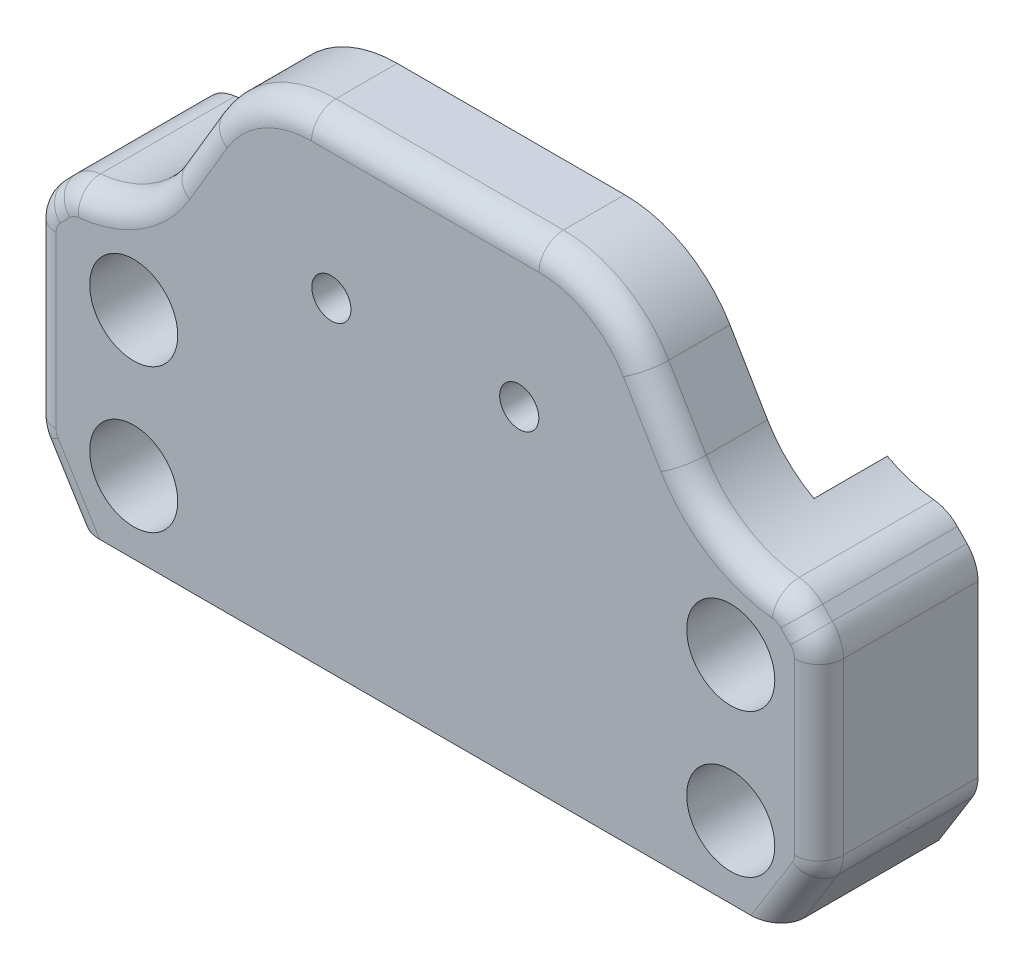
SolidWorks part; units mm, degrees
ref_plane "Front Plane" through (0, 0, 0) normal (0, 0, 1) x (1, 0, 0)
ref_plane "Top Plane" through (0, 0, 0) normal (0, 1, 0) x (1, 0, 0)
ref_plane "Right Plane" through (0, 0, 0) normal (1, 0, 0) x (0, 0, -1)
sketch "Sketch1" plane through (0, 0, 0) normal (0, 0, 1) x (1, 0, 0)
  line L16 (-28.9734, 12.7063) -> (28.9734, 12.7063)
  line L17 (32.1764, 18.7493) -> (32.1764, 32.6525)
  line L18 (31.2778, 34.8604) -> (30.4873, 35.6749)
  line L19 (20.9709, 41.4652) -> (17.9035, 46.6518)
  line L20 (9.2961, 51.5614) -> (-9.2961, 51.5614)
  line L21 (-17.9035, 46.6518) -> (-20.9709, 41.4652)
  line L22 (-30.4873, 35.6749) -> (-31.2778, 34.8604)
  line L23 (-32.1764, 32.6525) -> (-32.1764, 18.7493)
  arc A16 (-31.7074, 17.1064) -> (-28.9734, 12.7063) centre (10325.6911, 6449.6777) ccw
  arc A17 (28.9734, 12.7063) -> (31.7074, 17.1064) centre (-10325.6909, 6449.6776) ccw
  arc A18 (30.4873, 35.6749) -> (28.5623, 36.6074) centre (28.2447, 33.4985) ccw
  arc A19 (20.9709, 41.4652) -> (28.5623, 36.6074) centre (29.5783, 46.5556) ccw
  arc A20 (17.9035, 46.6518) -> (9.2961, 51.5614) centre (9.2961, 41.5614) ccw
  arc A21 (-9.2961, 51.5614) -> (-17.9035, 46.6518) centre (-9.2961, 41.5614) ccw
  arc A22 (-28.5623, 36.6074) -> (-20.9709, 41.4652) centre (-29.5783, 46.5556) ccw
  arc A23 (-28.5623, 36.6074) -> (-30.4873, 35.6749) centre (-28.2447, 33.4985) ccw
  spline S8 degree 3 poles (31.7074, 17.1064) (31.8606, 17.353) (31.9771, 17.6159) (32.1365, 18.1743) (32.1764, 18.459) (32.1764, 18.7493) knots 0 0 0 0 0.5 0.5 1 1 1 1
  spline S9 degree 3 poles (32.1764, 32.6525) (32.1764, 33.0639) (32.0982, 33.461) (31.8658, 34.0322) (31.7712, 34.2121) (31.5493, 34.5519) (31.4211, 34.7127) (31.2778, 34.8604) knots 0 0 0 0 0.5 0.5 0.75 0.75 1 1 1 1
  spline S10 degree 3 poles (-31.2778, 34.8604) (-31.5643, 34.5651) (-31.7861, 34.2264) (-32.0193, 33.6555) (-32.0775, 33.4608) (-32.156, 33.0628) (-32.1764, 32.8582) (-32.1764, 32.6525) knots 0 0 0 0 0.5 0.5 0.75 0.75 1 1 1 1
  spline S11 degree 3 poles (-32.1764, 18.7493) (-32.1764, 18.459) (-32.1365, 18.1742) (-31.9771, 17.6159) (-31.8606, 17.353) (-31.7074, 17.1064) knots 0 0 0 0 0.5 0.5 1 1 1 1
extrude "Boss-Extrude1" add sketch "Sketch1" along normal blind 13
shell "Shell1" thickness 3 removed face at (-0.0757, 32.8443, 0)
sketch "Sketch6" plane through (0, 0, 0) normal (0, 0, -1) x (-1, 0, 0)
  line L0 (-18.5324, 45.5884) -> (-18.5324, 12.7063)
  line L1 (28.9734, 12.7063) -> (18.5324, 12.7063)
  line L2 (32.1764, 32.6525) -> (32.1764, 18.7493)
  line L3 (30.4873, 35.6749) -> (31.2778, 34.8604)
  line L5 (18.5324, 45.5884) -> (20.9709, 41.4652)
  line L15 (18.5324, 45.5884) -> (18.5324, 12.7063)
  line L19 (32.1764, 18.7493) -> (32.1764, 32.6525)
  line L20 (31.2778, 34.8604) -> (30.4873, 35.6749)
  line L21 (20.9709, 41.4652) -> (17.9035, 46.6518)
  line L22 (9.2961, 51.5614) -> (-9.2961, 51.5614)
  line L23 (-17.9035, 46.6518) -> (-20.9709, 41.4652)
  line L24 (-30.4873, 35.6749) -> (-31.2778, 34.8604)
  line L25 (-32.1764, 32.6525) -> (-32.1764, 18.7493)
  line L26 (-28.9734, 12.7063) -> (28.9734, 12.7063)
  line L32 (-30.4873, 35.6749) -> (-31.2778, 34.8604)
  line L33 (-32.1764, 32.6525) -> (-32.1764, 18.7493)
  line L34 (-28.9734, 12.7063) -> (-18.5324, 12.7063)
  line L39 (-18.5324, 45.5884) -> (-20.9709, 41.4652)
  arc A0 (31.7074, 17.1064) -> (28.9734, 12.7063) centre (-10325.6909, 6449.6776) cw
  arc A1 (28.5623, 36.6074) -> (30.4873, 35.6749) centre (28.2447, 33.4985) cw
  arc A3 (28.5623, 36.6074) -> (20.9709, 41.4652) centre (29.5783, 46.5556) cw
  arc A24 (30.4873, 35.6749) -> (28.5623, 36.6074) centre (28.2447, 33.4985) ccw
  arc A25 (20.9709, 41.4652) -> (28.5623, 36.6074) centre (29.5783, 46.5556) ccw
  arc A27 (17.9035, 46.6518) -> (9.2961, 51.5614) centre (9.2961, 41.5614) ccw
  arc A28 (-28.5623, 36.6074) -> (-20.9709, 41.4652) centre (-29.5783, 46.5556) ccw
  arc A29 (-28.5623, 36.6074) -> (-30.4873, 35.6749) centre (-28.2447, 33.4985) ccw
  arc A30 (-31.7074, 17.1064) -> (-28.9734, 12.7063) centre (10325.6909, 6449.6776) ccw
  arc A31 (28.9734, 12.7063) -> (31.7074, 17.1064) centre (-10325.6911, 6449.6777) ccw
  arc A36 (-28.5623, 36.6074) -> (-20.9709, 41.4652) centre (-29.5783, 46.5556) ccw
  arc A37 (-28.5623, 36.6074) -> (-30.4873, 35.6749) centre (-28.2447, 33.4985) ccw
  arc A38 (-31.7074, 17.1064) -> (-28.9734, 12.7063) centre (10325.6909, 6449.6776) ccw
  arc A41 (-9.2961, 51.5614) -> (-17.9035, 46.6518) centre (-9.2961, 41.5614) ccw
  spline S0 degree 3 poles (32.1764, 18.7493) (32.1764, 18.459) (32.1365, 18.1743) (31.9771, 17.6159) (31.8606, 17.353) (31.7074, 17.1064) knots 0 0 0 0 0.5 0.5 1 1 1 1
  spline S1 degree 3 poles (31.2778, 34.8604) (31.4211, 34.7127) (31.5493, 34.5519) (31.7712, 34.2121) (31.8658, 34.0322) (32.0982, 33.461) (32.1764, 33.0639) (32.1764, 32.6525) knots 0 0 0 0 0.25 0.25 0.5 0.5 1 1 1 1
  spline S6 degree 3 poles (-912.5791, 346.2308) (-318.4122, 113.0842) (24.4464, -8.7582) (39.2445, 43.0679) (-277.4576, 113.683) (-947.6945, 218.3407) knots -47.236117 -47.236117 -47.236117 -47.236117 0.5 0.5 45.584579 45.584579 45.584579 45.584579 only from (31.7074, 17.1064) to (32.1764, 18.7493)
  spline S7 degree 3 poles (-468.469, 898.3041) (-31.3897, -10.7843) (34.4741, 21.3175) (32.0775, 33.4608) (32.0193, 33.6555) (21.9253, 58.367) (-263.5849, -90.6627) (-388.758, -872.6435) knots -14.755305 -14.755305 -14.755305 -14.755305 0.25 0.25 0.5 0.5 32.717715 32.717715 32.717715 32.717715 only from (32.1764, 32.6525) to (31.2778, 34.8604)
  spline S8 degree 3 poles (-1112.7848, -2759.5108) (116.981, -4.4034) (-22.0681, 49.0741) (-31.7712, 34.2121) (-31.8658, 34.0322) (-45.7307, -0.0443) (547.9859, -163.1479) (2818.0682, 896.9495) knots -21.365975 -21.365975 -21.365975 -21.365975 0.25 0.25 0.5 0.5 44.99757 44.99757 44.99757 44.99757 only from (-31.2778, 34.8604) to (-32.1764, 32.6525)
  spline S9 degree 3 poles (2916.7276, 565.2774) (892.1774, 236.9438) (-44.3588, 60.9799) (-18.3881, -29.9762) (1076.9235, 400.8267) (2716.3284, 1214.7036) knots -76.665281 -76.665281 -76.665281 -76.665281 0.5 0.5 86.237754 86.237754 86.237754 86.237754 only from (-32.1764, 18.7493) to (-31.7074, 17.1064)
  spline S12 degree 3 poles (-31.2778, 34.8604) (-31.4211, 34.7127) (-31.5493, 34.5519) (-31.7712, 34.2121) (-31.8658, 34.0322) (-32.0982, 33.461) (-32.1764, 33.0639) (-32.1764, 32.6525) knots 0 0 0 0 0.25 0.25 0.5 0.5 1 1 1 1
  spline S13 degree 3 poles (-32.1764, 18.7493) (-32.1764, 18.459) (-32.1365, 18.1743) (-31.9771, 17.6159) (-31.8606, 17.353) (-31.7074, 17.1064) knots 0 0 0 0 0.5 0.5 1 1 1 1
  point P15 (-18.5324, 29.1474)
  point P22 (18.5324, 29.1474)
  point P51 (-18.5324, 29.1474)
  dimension "D1" = 0
extrude "Boss-Extrude4" add sketch "Sketch6" against normal up to surface (10 mm away) up to face at (0.001, 31.9038, 10)
sketch "Sketch3" plane through (0, 51.5614, 0) normal (0, 1, 0) x (1, 0, 0)
  line L0 (-24.7666, 0) -> (-24.7666, -6)
  line L1 (-20.9709, 0) -> (-28.5623, 0) construction
  line L2 (-24.7666, -6) -> (24.7666, -6)
  line L3 (24.7666, 0) -> (24.7666, -6)
  line L4 (28.5623, 0) -> (20.9709, 0) construction
  line L5 (24.7666, 0) -> (-24.7666, 0)
extrude "Cut-Extrude1" cut sketch "Sketch3" against normal blind 15
sketch "Sketch4" plane through (0, 0, 13) normal (0, 0, 1) x (1, 0, 0)
  circle A0 centre (7.6788, 39.2392) radius 1.6
  circle A5 centre (-7.6788, 39.2392) radius 1.6
extrude "Cut-Extrude2" cut sketch "Sketch4" against normal through all
sketch "Sketch7" plane through (0, 0, 0) normal (0, 0, -1) x (-1, 0, 0)
  circle A0 centre (23.8343, 30.3308) radius 2.1
  circle A10 centre (23.8343, 18.5863) radius 2.1237
  circle A11 centre (-24.9657, 18.5863) radius 2.1
  circle A12 centre (-24.9657, 30.3308) radius 2.1
extrude "Cut-Extrude3" cut sketch "Sketch7" against normal through all
fillet "Fillet2" radius 10 2 edges at (18.5324, 36.5614, 3) (-18.5324, 36.5614, 3)
sketch "Sketch9" plane through (0, 0, 13) normal (0, 0, 1) x (1, 0, 0)
  circle A0 centre (-23.8343, 18.5863) radius 3.6
  circle A1 centre (-23.8343, 30.3308) radius 3.6
  circle A2 centre (24.9657, 18.5863) radius 3.6
  circle A3 centre (24.9657, 30.3308) radius 3.6
extrude "Cut-Extrude4" cut sketch "Sketch9" against normal blind 10
fillet "Fillet3" radius 2 19 edges at (29.607, 36.311, 13) (24.1883, 38.1326, 13) (19.4372, 44.0585, 13) (14.2507, 50.2477, 13) (0, 51.5614, 13) (-14.2507, 50.2477, 13) (-19.4372, 44.0585, 13) (-24.1883, 38.1326, 13) (-29.607, 36.311, 13)
fillet "Fillet4" radius 2 2 edges at (-18.5324, 15.7063, 5) (18.5324, 15.7063, 5)
